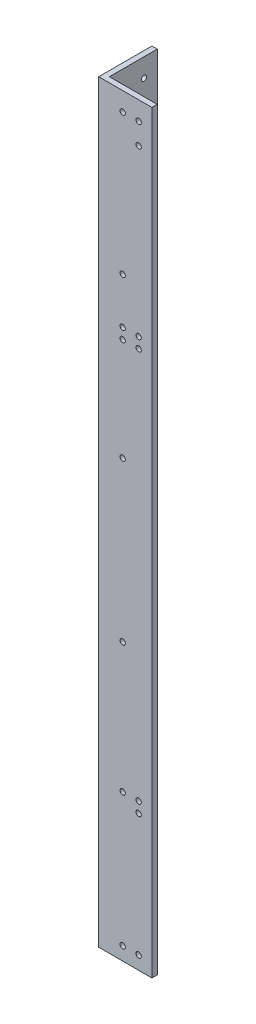
SolidWorks part; units mm, degrees
ref_plane "Front Plane" through (0, 0, 0) normal (0, 0, 1) x (1, 0, 0)
ref_plane "Top Plane" through (0, 0, 0) normal (0, 1, 0) x (1, 0, 0)
ref_plane "Right Plane" through (0, 0, 0) normal (1, 0, 0) x (0, 0, -1)
sketch "Sketch2" plane through (0, 0, 0) normal (0, 1, 0) x (1, 0, 0)
  line L0 (0, 31.75) -> (3.175, 31.75)
  line L1 (3.175, 31.75) -> (3.175, 3.175)
  line L2 (3.175, 3.175) -> (31.75, 3.175)
  line L3 (31.75, 3.175) -> (31.75, 0)
  line L4 (31.75, 0) -> (0, 0)
  line L5 (0, 0) -> (0, 31.75)
  point P9 (1.5875, 31.75)
  point P10 (31.75, 1.5875)
  dimension "D4" = 3.175
  dimension "D1" = 31.75
  dimension "D2" = 31.75
  dimension "D3" = 3.175
extrude "Boss-Extrude1" add sketch "Sketch2" along normal blind 450
sketch "BackSideHoles-Sketch3" plane through (0, 0, 0) normal (0, 0, 1) x (1, 0, 0)
  line L0 (0, 0) -> (31.75, 0) construction
  line L1 (0, 450) -> (0, 0) construction
  circle A1 centre (23.8125, 81.1125) radius 1.5875
  circle A2 centre (14.2875, 87.4625) radius 1.5875
  circle A3 centre (23.8125, 87.4625) radius 1.5875
  circle A4 centre (14.2875, 438.8875) radius 1.5875
  circle A6 centre (23.8125, 438.8875) radius 1.5875
  circle A7 centre (23.8125, 426.1875) radius 1.5875
  circle A10 centre (14.2875, 327.6026) radius 1.5875
  circle A11 centre (23.8125, 327.6026) radius 1.5875
  circle A12 centre (14.2875, 321.2526) radius 1.5875
  circle A13 centre (23.8125, 321.2526) radius 1.5875
  circle A14 centre (14.2875, 165) radius 1.5875
  circle A15 centre (14.2875, 260) radius 1.5875
  circle A16 centre (14.2875, 355) radius 1.5875
  circle A17 centre (14.2875, 7.9375) radius 1.5875
  circle A18 centre (23.8125, 7.9375) radius 1.5875
  dimension "D4" = 3.175
  dimension "D8" = 11.1125
  dimension "D7" = 6.35
  dimension "D10" = 327.6026
  dimension "D11" = 165
  dimension "D12" = 95
  dimension "D13" = 95
  dimension "D6" = 7.9375
  dimension "D5" = 6.35
  dimension "D14" = 81.1125
  dimension "D3" = 9.525
  dimension "D2" = 14.2875
  dimension "D9" = 12.7
sketch "RightSideHoles-Sketch4" plane through (0, 0, 0) normal (-1, 0, 0) x (0, 0, 1)
  line L0 (-31.75, 450) -> (0, 450) construction
  line L1 (0, 450) -> (0, 0) construction
  line L3 (-31.75, 0) -> (0, 0) construction
  circle A0 centre (-23.8125, 81.1125) radius 1.5875
  circle A2 centre (-23.8125, 87.4625) radius 1.5875
  circle A4 centre (-23.8125, 438.8875) radius 1.5875
  circle A5 centre (-14.2875, 426.1875) radius 1.5875
  circle A6 centre (-23.8125, 426.1875) radius 1.5875
  circle A10 centre (-23.8125, 327.6026) radius 1.5875
  circle A11 centre (-14.2875, 327.6026) radius 1.5875
  circle A12 centre (-23.8125, 292.6776) radius 1.5875
  circle A13 centre (-14.2875, 292.6776) radius 1.5875
  circle A14 centre (-23.8125, 7.9375) radius 1.5875
  circle A15 centre (-14.2875, 7.9375) radius 1.5875
  circle A16 centre (-14.2875, 165) radius 1.5875
  circle A17 centre (-14.2875, 260) radius 1.5875
  circle A18 centre (-14.2875, 355) radius 1.5875
  circle A19 centre (-14.2875, 81.1125) radius 1.5875
  dimension "D4" = 3.175
  dimension "D10" = 327.6026
  dimension "D13" = 95
  dimension "D5" = 6.35
  dimension "D2" = 14.2875
  dimension "D6" = 11.1125
  dimension "D8" = 7.9375
  dimension "D9" = 34.925
  dimension "D7" = 12.7
  dimension "D12" = 165
  dimension "D14" = 95
  dimension "D3" = 81.1125
  dimension "D11" = 9.525
extrude "BackSideHoles-Cut-Extrude1" cut sketch "BackSideHoles-Sketch3" against normal blind 3.175
extrude "RightSideHoles-Cut-Extrude2" cut sketch "RightSideHoles-Sketch4" against normal blind 3.175
equation "\"RailThickness\"= .125in'Spec"
equation "\"VSWidth\"= 1.25in'Spec"
equation "\"VSHeight\"= 1.25in'Spec"
equation "\"VSLength\"= 450mm"
equation "\"HoleOffsetFromEdge\"= \"RailThickness\" * 2.5"
equation "\"HoleOffsetFromSide\"= \"RailThickness\" * 3.5"
equation "\"LegHeight\"= 70mm'Space needed for PSU/Stepper/Electronics"
equation "\"VSBottomSideRailHoleY1FromBottomOfLowerRail\"= \"V1 BottomOfLowerRail\" + \"HoleOffsetFromSide\"'Equals 70.1125"
equation "\"VSSideRailHoleX1FromSide\"= \"HoleOffsetFromSide\" + \"RailThickness\""
equation "\"FasteningHoleDiameter\"= .125in"
equation "\"VSBottomSideRailHoleY2FromY1\" = \"LowerRailHeight\" - \"HoleOffsetFromSide\" - \"HoleOffsetFromEdge\"'Equals 6.35"
equation "\"VSTopSideRailHoleY1FromEdge\"= \"HoleOffsetFromEdge\" + \"RailThickness\""
equation "\"D4@BackSideHoles-Sketch3\" = \"FasteningHoleDiameter\""
equation "\"D1@Boss-Extrude1\"=\"VSLength\""
equation "\"D4@RightSideHoles-Sketch4\"=\"FasteningHoleDiameter\""
equation "\"D8@BackSideHoles-Sketch3\" = \"VSTopSideRailHoleY1FromEdge\""
equation "\"D6@RightSideHoles-Sketch4\"=\"VSTopSideRailHoleY1FromEdge\""
equation "\"VSMidSideRailHoleY1FromV8TopOfMidSideRail\"= \"V8 ToTopOfMidSideRail\" - \"HoleOffsetFromEdge\"'Equals 308.2875"
equation "\"LowerRailHeight\"= 1.00in"
equation "\"D2@Sketch2\"=\"VSWidth\""
equation "\"D1@Sketch2\"=\"VSHeight\""
equation "\"MidBackRailHeight\"= 1.00in"
equation "\"VSMidBackRailHoleY1FromV7TopOfMidBackRail\"= \"V7 ToTopOfMidBackRail\" - \"HoleOffsetFromSide\"'Equals 308.2875"
equation "\"TopRailHeight\"= 1.25in"
equation "\"MidLeftOrRightSideRailHeight\"= 2.0in"
equation "\"D8@RightSideHoles-Sketch4\"=\"HoleOffsetFromEdge\""
equation "\"VSMidBackRailHoleY2FromY1\"= \"MidBackRailHeight\" - \"HoleOffsetFromSide\" - \"HoleOffsetFromEdge\"'Equals 6.35"
equation "\"VSMidSideRailHoleY2FromY1\"= \"MidLeftOrRightSideRailHeight\" - \"HoleOffsetFromEdge\" * 2'Equals 34.925"
equation "\"D7@BackSideHoles-Sketch3\"=\"VSMidBackRailHoleY2FromY1\""
equation "\"D9@RightSideHoles-Sketch4\"=\"VSMidSideRailHoleY2FromY1\""
equation "\"VSTopSideRailHoleY2FromY1\"= \"TopRailHeight\" - \"VSTopSideRailHoleY1FromEdge\" - \"HoleOffsetFromEdge\"'Equals 12.7"
equation "\"VSSideRailHoleX2FromX1\"= \"VSWidth\" - \"VSSideRailHoleX1FromSide\" - \"HoleOffsetFromEdge\""
equation "\"D7@RightSideHoles-Sketch4\"=\"VSTopSideRailHoleY2FromY1\""
equation "\"V1 BottomOfLowerRail\"= \"LegHeight\""
equation "\"StepperShaftLength\"= 24mm'Pulley will be attached to the end"
equation "\"ZAxisLeadScrewLength\"= 200mm"
equation "\"HotEndToTopOfXAxisGB\"= 63.315144mm'Measured from the100.Should be 63.315144"
equation "\"TopOfGBToBottomOfLinearRail\"= \"LinearGBWidth\" / 2 + \"LinearRailWidth\" / 2"
equation "\"LinearGBWidth\"= 27mm'Spec"
equation "\"V5 ToBottomOfXAxisLinearRail\"= \"V4 ToTopOfBuildPlate/HotEndTip\" + \"HotEndToTopOfXAxisGB\" - \"TopOfGBToBottomOfLinearRail\""
equation "\"LinearRailWidth\"= 12mm'Spec"
equation "\"V6 ToBottomOfGantryPulley\"= \"V5 ToBottomOfXAxisLinearRail\" - \"DistanceFromGABTopToLowerPulley\""
equation "\"GABUpperHeight\"= 6mm"
equation "\"GABMidWallHeight\"= 28mm'Must equal 28 or changes alignment"
equation "\"20TGT2PulleyWidth\"= 8.7mm'The STL of the Pulley in the diagram is a bit larger"
equation "\"GABMidShortRiserHeight\"= \"GABMidWallHeight\" / 2 - \"20TGT2PulleyWidth\"'Equals 5.3"
equation "\"GABRiserBossOffset\"= 0.8mm'Aligns Pulleys"
equation "\"DistanceFromGABTopToLowerPulley\"= \"GABUpperHeight\" + \"GABMidWallHeight\" - \"GABMidShortRiserHeight\" + \"GABRiserBossOffset\" / 2"
equation "\"V7 ToTopOfMidBackRail\"= \"V6 ToBottomOfGantryPulley\" + \"StepperShaftLength\""
equation "\"D10@BackSideHoles-Sketch3\" = \"VSMidBackRailHoleY1FromV7TopOfMidBackRail\""
equation "\"D10@RightSideHoles-Sketch4\"=\"VSMidSideRailHoleY1FromV8TopOfMidSideRail\""
equation "\"BedToBuildPlateStandoffLength\"= 15mm"
equation "\"BuildPlateHeight\"= 8mm'Spec"
equation "\"V4 ToTopOfBuildPlate/HotEndTip\"= \"V2 ToBedAtTopOfZAxis\" + \"BedToBuildPlateStandoffLength\" + \"BuildPlateHeight\""
equation "\"V2 ToBedAtTopOfZAxis\"= \"V1 BottomOfLowerRail\" - \"LowerEnclosureThickness\" + \"StepperShaftLength\" + \"ZAxisLeadScrewLength\" - \"LM8UUHeight\" / 2"
equation "\"LM8UUHeight\"= 24mm'Spec"
equation "\"V8 ToTopOfMidSideRail\"= \"V7 ToTopOfMidBackRail\" - \"RailThickness\""
equation "\"VSEnclosureOffsets\"= ( \"VSLength\" - \"LegHeight\" ) / 4"
equation "\"D11@BackSideHoles-Sketch3\"=\"LegHeight\" + \"VSEnclosureOffsets\""
equation "\"D12@BackSideHoles-Sketch3\"=\"VSEnclosureOffsets\""
equation "\"D13@BackSideHoles-Sketch3\"=\"VSEnclosureOffsets\""
equation "\"D12@RightSideHoles-Sketch4\"=\"LegHeight\" + \"VSEnclosureOffsets\""
equation "\"D13@RightSideHoles-Sketch4\"=\"VSEnclosureOffsets\""
equation "\"D14@RightSideHoles-Sketch4\"=\"VSEnclosureOffsets\""
equation "\"D6@BackSideHoles-Sketch3\"=\"HoleOffsetFromEdge\""
equation "\"D5@BackSideHoles-Sketch3\"=\"VSBottomSideRailHoleY2FromY1\""
equation "\"D14@BackSideHoles-Sketch3\"=\"VSBottomSideRailHoleY1FromBottomOfLowerRail\""
equation "\"D2@BackSideHoles-Sketch3\"=\"VSSideRailHoleX1FromSide\""
equation "\"D9@BackSideHoles-Sketch3\"=\"VSTopSideRailHoleY2FromY1\""
equation "\"D3@RightSideHoles-Sketch4\"=\"VSBottomSideRailHoleY1FromBottomOfLowerRail\""
equation "\"D5@RightSideHoles-Sketch4\"=\"VSBottomSideRailHoleY2FromY1\""
equation "\"D2@RightSideHoles-Sketch4\"=\"VSSideRailHoleX1FromSide\""
equation "\"D11@RightSideHoles-Sketch4\"=\"VSSideRailHoleX2FromX1\""
equation "\"LowerEnclosureThickness\"= 5mm"
